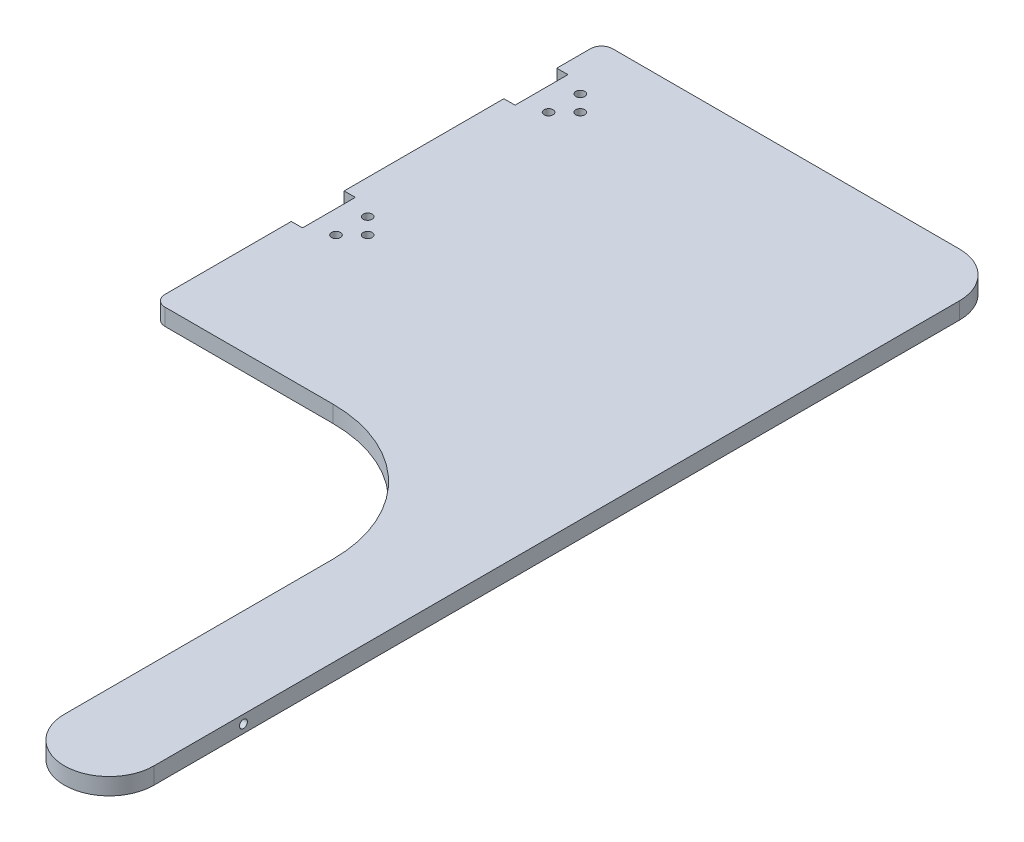
SolidWorks part; units mm, degrees
ref_plane "Front Plane" through (0, 0, 0) normal (0, 0, 1) x (1, 0, 0)
ref_plane "Top Plane" through (0, 0, 0) normal (0, 1, 0) x (1, 0, 0)
ref_plane "Right Plane" through (0, 0, 0) normal (1, 0, 0) x (0, 0, -1)
sketch "Sketch1" plane through (0, 0, 0) normal (0, 1, 0) x (1, 0, 0)
  line L1 (6.35, 0) -> (101.6, 0)
  line L2 (0, 6.35) -> (0, 247.65)
  line L3 (6.35, 254) -> (203.2, 254)
  line L6 (228.6, 228.6) -> (228.6, -228.6)
  line L8 (177.8, -76.2) -> (177.8, -228.6)
  arc A0 (177.8, -76.2) -> (101.6, 0) centre (101.6, -76.2) ccw
  arc A3 (228.6, 228.6) -> (203.2, 254) centre (203.2, 228.6) ccw
  arc A4 (0, 6.35) -> (6.35, 0) centre (6.35, 6.35) ccw
  arc A5 (0, 247.65) -> (6.35, 254) centre (6.35, 247.65) cw
  arc A6 (228.6, -228.6) -> (177.8, -228.6) centre (203.2, -228.6) cw
  point P9 (0, 0)
  point P10 (0, 0)
  point P17 (228.6, 254)
  point P20 (0, 0)
  point P23 (0, 254)
  dimension "D5" = 76.2
  dimension "D7" = 6.35
  dimension "D3" = 25.4
  dimension "D4" = 482.6
  dimension "D1" = 254
  dimension "D2" = 228.6
extrude "Boss-Extrude1" add sketch "Sketch1" along normal blind 9.525
sketch "Sketch2" plane through (0, 9.525, 0) normal (0, 1, 0) x (1, 0, 0)
  line L0 (0, 247.65) -> (0, 6.35) construction
  line L1 (0, 228.6) -> (6.35, 228.6)
  line L2 (0, 228.6) -> (0, 198.6)
  line L3 (0, 198.6) -> (6.35, 198.6)
  line L4 (6.35, 228.6) -> (6.35, 198.6)
  line L5 (203.2, 254) -> (6.35, 254) construction
  line L19 (6.35, 213.6) -> (63.5487, 213.6) construction
  line L28 (0, 107.95) -> (6.35, 107.95)
  line L33 (0, 107.95) -> (0, 77.95)
  line L34 (0, 77.95) -> (6.35, 77.95)
  line L35 (6.35, 107.95) -> (6.35, 77.95)
  line L36 (6.35, 92.95) -> (63.5487, 92.95) construction
  circle A1 centre (28.35, 213.6) radius 2.54
  circle A2 centre (19.35, 222.6) radius 2.54
  circle A3 centre (19.35, 204.6) radius 2.54
  circle A13 centre (28.35, 92.95) radius 2.54
  circle A14 centre (19.35, 101.95) radius 2.54
  circle A15 centre (19.35, 83.95) radius 2.54
  dimension "D3" = 28.35
  dimension "D4" = 5.08
  dimension "D5" = 19.35
  dimension "D6" = 9
  dimension "D1" = 30
  dimension "D2" = 25.4
  dimension "D7" = 2
  dimension "D8" = 6.35
  dimension "D9" = 120.65
extrude "Cut-Extrude1" cut sketch "Sketch2" against normal up to next
sketch "Sketch3" plane through (228.6, 0, 0) normal (1, 0, 0) x (0, 0, -1)
  line L0 (-254, 9.525) -> (-254, 0) construction
  line L1 (-228.6, 0) -> (228.6, 0) construction
  circle A0 centre (-177.8, 4.7625) radius 2.2479
  dimension "D2" = 4.4958
  dimension "D3" = 4.7625
  dimension "D1" = 76.2
extrude "Cut-Extrude2" cut sketch "Sketch3" against normal up to next
